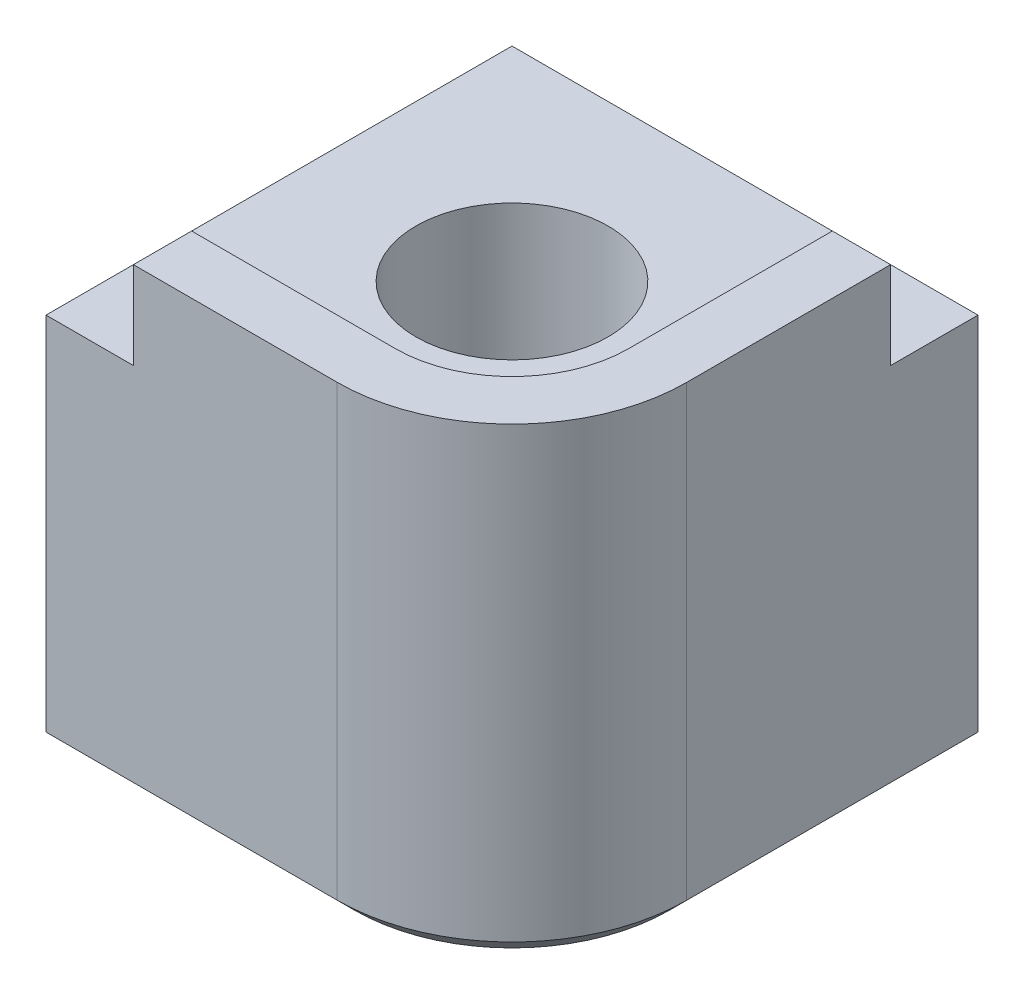
SolidWorks part; units mm, degrees
ref_plane "Front Plane" through (0, 0, 0) normal (0, 0, 1) x (1, 0, 0)
ref_plane "Top Plane" through (0, 0, 0) normal (0, 1, 0) x (1, 0, 0)
ref_plane "Right Plane" through (0, 0, 0) normal (1, 0, 0) x (0, 0, -1)
sketch "Base" plane through (0, 0, 0) normal (0, 1, 0) x (1, 0, 0)
  line L1 (-4, -4) -> (4, -4)
  line L2 (-4, -4) -> (-4, 4)
  line L3 (-4, 4) -> (4, 4)
  line L4 (4, -4) -> (4, 4)
  line L5 (-4, -4) -> (4, 4) construction
  line L6 (-4, 4) -> (4, -4) construction
  point P0 (0, 0)
  dimension "D1" = 8
  dimension "D2" = 8
extrude "Boss-Extrude1" add sketch "Base" against normal blind 8
sketch "Cutout" plane through (0, 0, 0) normal (0, 1, 0) x (1, 0, 0)
  line L1 (-4, 4) -> (3, 4)
  line L2 (-4, 4) -> (-4, -3)
  line L3 (-4, -3) -> (3, -3)
  line L4 (3, 4) -> (3, -3)
  line L5 (3, -3) -> (-4, 4) construction
  line L6 (3, 4) -> (-4, -3) construction
  point P5 (-0.5, 0.5)
  point P6 (0, 0)
  point P7 (0, 0)
  dimension "D1" = 7
  dimension "D2" = 7
extrude "Cut-Extrude1" cut sketch "Cutout" against normal blind 1.5
sketch "Sketch3" plane through (3, 0, 0) normal (-1, 0, 0) x (0, 0, 1)
  line L0 (3, -1.5) -> (-4, -1.5) construction
  line L1 (-4, 0) -> (-2.5, 0)
  line L2 (-4, 0) -> (-4, -1.5)
  line L3 (-4, -1.5) -> (-2.5, -1.5)
  line L4 (-2.5, 0) -> (-2.5, -1.5)
  dimension "D1" = 1.5
extrude "Cut-Extrude2" cut sketch "Sketch3" against normal through all
ref_axis "Axis2" through (3, -1.5, 3) along (-0.7071, 0, -0.7071)
ref_plane "Plane1" through (0, 0, 0) normal (0.7071, 0, -0.7071) x (-0.7071, 0, -0.7071)
mirror "Mirror1" about plane through (0, 0, 0) normal (0.7071, 0, -0.7071) of "Cut-Extrude2"
fillet "Fillet3" radius 2 1 edges at (3, -0.75, 3)
fillet "Fillet4" radius 3 1 edges at (4, -4, 4)
hole_wizard "M4 Tapped Hole1" positions "Sketch12" profile "Sketch13" tap size "M4" standard "AS" end condition through all
sketch "Sketch12" plane through (0, -1.5, 0) normal (0, 1, 0) x (1, 0, 0)
  line L0 (4, 4) -> (-4, 4) construction
  line L1 (-4, 4) -> (-4, -4) construction
  point P0 (-0.5, 0.5)
  dimension "D1" = 3.5
  dimension "D2" = 3.5
cosmetic thread "Hole Thread1" parameters "D2"=4
sketch "Sketch13" plane through (-0.5, -1.5, -0.5) normal (1, 0, 0) x (0, 0, 1)
  line L0 (0, 0) -> (0, 6.5)
  line L1 (0, 6.5) -> (1.65, 6.5)
  line L2 (1.65, 6.5) -> (1.65, 0)
  line L5 (1.65, 0) -> (0, 0)
  line L11 (0, -6.35) -> (0, 107.95) construction
  dimension "Thru Tap Drill Dia." = 3.3
  dimension "Thru Tap Drill Depth" = 6.5
chamfer "Chamfer1" distance 0.3 angle 45 5 edges at (-4, -8, 0) (-1.5, -8, 4) (3.1213, -8, 3.1213) (4, -8, -1.5) (0, -8, -4)
